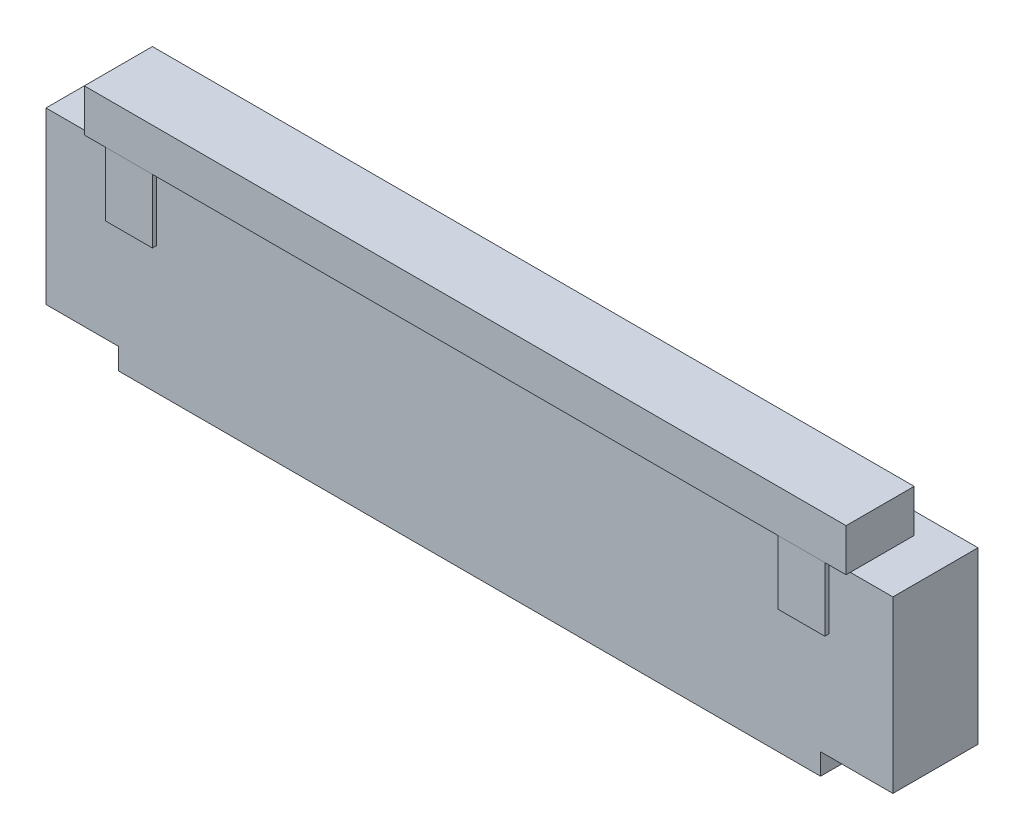
SolidWorks part; units mm, degrees
other "Детальный элемент1"
ref_plane "Спереди" through (0, 0, 0) normal (0, 0, 1) x (1, 0, 0)
ref_plane "Сверху" through (0, 0, 0) normal (0, 1, 0) x (1, 0, 0)
ref_plane "Справа" through (0, 0, 0) normal (1, 0, 0) x (0, 0, -1)
sketch "Эскиз1" plane through (0, 0, 0) normal (0, 0, 1) x (1, 0, 0)
  line L1 (0, -4.5) -> (9.95, -4.5)
  line L2 (0, -4.5) -> (0, 0)
  line L3 (0, 0) -> (9.95, 0)
  line L4 (9.95, -4.5) -> (9.95, 0)
  dimension "D1" = 9.95
  dimension "D2" = 4.5
extrude "Бобышка-Вытянуть1" add sketch "Эскиз1" along normal blind 2
sketch "Эскиз3" plane through (0, -4.5, 0) normal (0, -1, 0) x (1, 0, 0)
  line L0 (0, 0) -> (9.95, 0) construction
  line L1 (9.95, 2) -> (8.25, 2)
  line L2 (9.95, 2) -> (9.95, 0.6)
  line L3 (9.95, 0.6) -> (8.25, 0.6)
  line L4 (8.25, 2) -> (8.25, 0.6)
  dimension "D1" = 1.7
  dimension "D2" = 0.6
extrude "Вырез-Вытянуть1" cut sketch "Эскиз3" against normal blind 0.5
sketch "Эскиз4" plane through (0, -4.5, 0) normal (0, -1, 0) x (1, 0, 0)
  line L0 (0, 0) -> (9.95, 0) construction
  line L1 (9.95, 0.6) -> (8.95, 0.6)
  line L2 (9.95, 0.6) -> (9.95, 0)
  line L3 (9.95, 0) -> (8.95, 0)
  line L4 (8.95, 0.6) -> (8.95, 0)
  dimension "D1" = 1
extrude "Вырез-Вытянуть2" cut sketch "Эскиз4" against normal up to surface (0.5 mm away) up to face at (9.1, -4, 1.3)
sketch "Эскиз2" plane through (0, 0, 0) normal (0, 1, 0) x (1, 0, 0)
  line L0 (9.95, -2) -> (9.95, 0) construction
  line L1 (0, -2.1) -> (8.95, -2.1)
  line L2 (0, -2.1) -> (0, -0.5)
  line L3 (0, -0.5) -> (8.95, -0.5)
  line L4 (8.95, -2.1) -> (8.95, -0.5)
  line L5 (0, -2) -> (0, 0) construction
  line L6 (9.95, -2) -> (0, -2) construction
  dimension "D1" = 1.6
  dimension "D2" = 1
  dimension "D3" = 0.1
extrude "Бобышка-Вытянуть2" add sketch "Эскиз2" along normal blind 1 separate body
sketch "Эскиз5" plane through (0, 0, 0) normal (0, -1, 0) x (1, 0, 0)
  line L0 (0, 2.1) -> (8.95, 2.1) construction
  line L1 (8.45, 2.1) -> (7.35, 2.1)
  line L2 (8.45, 2.1) -> (8.45, 0.5)
  line L3 (8.45, 0.5) -> (7.35, 0.5)
  line L4 (7.35, 2.1) -> (7.35, 0.5)
  line L5 (8.95, 0.5) -> (0, 0.5) construction
  line L6 (9.95, 2) -> (9.95, 0) construction
  dimension "D1" = 1.5
  dimension "D2" = 1.1
extrude "Бобышка-Вытянуть3" add sketch "Эскиз5" along normal blind 1.5 separate body
mirror "Зеркальное отражение1" about plane through (0, -4.5, 2) normal (1, 0, 0) of bodies 108 110 111
combine bodies "Соединить5" operation type add bodies to combine 110 113
combine bodies "Соединить6" operation type add bodies to combine 112 108
sketch "Эскиз7" plane through (0, -4.5, 0) normal (0, -1, 0) x (1, 0, 0)
  line L6 (-8.95, 0) -> (8.95, 0) construction
  line L7 (6.9, 0) -> (7.1, 0)
  line L8 (6.9, 0) -> (6.9, 0.15)
  line L9 (6.9, 0.15) -> (7.1, 0.15)
  line L10 (7.1, 0) -> (7.1, 0.15)
  point P6 (7, 0)
  dimension "D1" = 7
  dimension "D2" = 0.15
  dimension "D3" = 0.2
extrude "Бобышка-Вытянуть4" add sketch "Эскиз7" along normal blind 0.7 separate body
pattern_linear "Линейный массив1" count 29 spacing 0.5 along (-1, 0, 0) of "Бобышка-Вытянуть4"
equation "\"N\"= 29"
equation "\"D1@Эскиз7\"=0.25*(\"N\"-1)"
